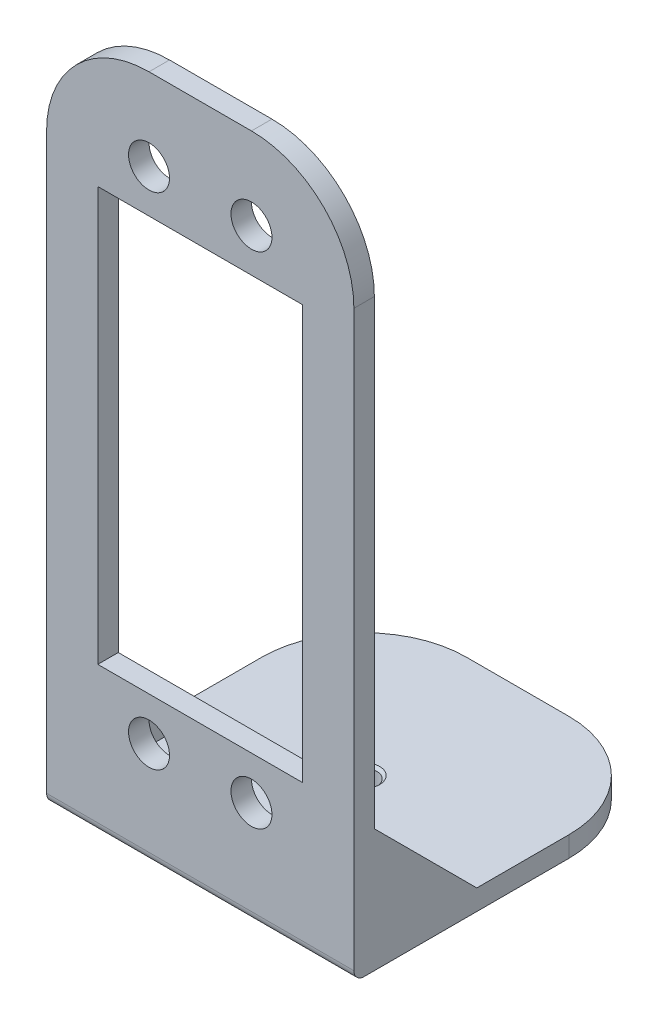
SolidWorks part; units mm, degrees
ref_plane "Front Plane" through (0, 0, 0) normal (0, 0, 1) x (1, 0, 0)
ref_plane "Top Plane" through (0, 0, 0) normal (0, 1, 0) x (1, 0, 0)
ref_plane "Right Plane" through (0, 0, 0) normal (1, 0, 0) x (0, 0, -1)
sketch "Sketch1" plane through (0, 0, 0) normal (0, 1, 0) x (1, 0, 0)
  line L1 (0, 0) -> (30, 0)
  line L2 (0, 0) -> (0, 30)
  line L3 (0, 30) -> (30, 30)
  line L4 (30, 0) -> (30, 30)
  dimension "D1" = 30
  dimension "D2" = 30
extrude "Boss-Extrude1" add sketch "Sketch1" along normal blind 2
sketch "Sketch2" plane through (0, 2, 0) normal (0, 1, 0) x (1, 0, 0)
  line L0 (30, 0) -> (30, 30) construction
  line L1 (0, 0) -> (30, 0)
  line L2 (0, 0) -> (0, 1)
  line L3 (0, 1) -> (30, 1)
  line L4 (30, 0) -> (30, 1)
  line L6 (0, 0) -> (30, 0)
  line L7 (0, 0) -> (0, -1)
  line L8 (0, -1) -> (30, -1)
  line L9 (30, 0) -> (30, -1)
  line M1 (0, 30) -> (0, 0)
  line M2 (0, 0) -> (30, 0)
  line M3 (30, 0) -> (30, 30)
  dimension "D1" = 1
  dimension "D2" = 1
extrude "Boss-Extrude2" add sketch "Sketch2" along normal blind 65 and the other way blind 2 contours L3 M1 M2 M3 | L9 L7 L8 M2 region at (15, 2, -0.5) region at (15, 2, 0.5)
fillet "Fillet1" radius 1 2 edges at (15, 0, 1) (15, 2, -1)
sketch "Sketch5" plane through (0, 2, 0) normal (0, 1, 0) x (1, 0, 0)
  line L0 (30, 2) -> (30, 30) construction
  line L1 (30, 30) -> (0, 30) construction
  circle A0 centre (15, 15) radius 1.5
  dimension "D1" = 15
  dimension "D2" = 15
hole_wizard "M3 Tapped Hole1" positions "Sketch6" profile "Sketch7" tap size "M3" standard "ISO" end condition through all
sketch "Sketch6" plane through (0, 2, 0) normal (0, 1, 0) x (1, 0, 0)
  point P0 (15, 15)
sketch "Sketch7" plane through (15, 2, -15) normal (1, 0, 0) x (0, 0, 1)
  line L0 (0, 0) -> (0, 2)
  line L1 (0, 2) -> (1.25, 2)
  line L2 (1.25, 2) -> (1.25, 0.275)
  line L3 (1.25, 0.275) -> (1.525, 0)
  line L5 (1.525, 0) -> (0, 0)
  line L6 (-1.25, 0.275) -> (-1.525, 0) construction
  line L11 (0, -6.35) -> (0, 107.95) construction
  dimension "Thru Tap Drill Dia." = 2.5
  dimension "Thru Tap Drill Depth" = 2
  dimension "Near C'Sink Dia." = 3.05
  dimension "Near C'Sink Angle" = 90
cosmetic thread "Hole Thread1" parameters "D2"=3
sketch "Sketch11" plane through (0, 0, 1) normal (0, 0, 1) x (1, 0, 0)
  line L0 (0, 1) -> (0, 67) construction
  line L1 (10, 59) -> (20, 59)
  line L2 (10, 59) -> (10, 10.2)
  line L3 (10, 10.2) -> (20, 10.2)
  line L4 (20, 59) -> (20, 10.2)
  line L5 (0, 67) -> (30, 67) construction
  line L6 (30, 3) -> (30, 67) construction
  line L7 (30, 0) -> (0, 0) construction
  line L8 (0, 54.8) -> (20, 54.8)
  line L9 (0, 54.8) -> (0, 14.4)
  line L10 (0, 14.4) -> (20, 14.4)
  line L11 (20, 54.8) -> (20, 14.4)
  line L13 (20, 54.8) -> (25, 54.8)
  line L14 (20, 54.8) -> (20, 14.4)
  line L15 (20, 14.4) -> (25, 14.4)
  line L16 (25, 54.8) -> (25, 14.4)
  line L17 (10, 14.4) -> (5, 14.4)
  line L18 (10, 14.4) -> (10, 54.8)
  line L19 (10, 54.8) -> (5, 54.8)
  line L20 (5, 14.4) -> (5, 54.8)
  circle A0 centre (10, 59) radius 2
  circle A1 centre (20, 59) radius 2
  circle A4 centre (10, 10.2) radius 2
  circle A5 centre (20, 10.2) radius 2
  dimension "D1" = 48.8
  dimension "D7" = 4.2
  dimension "D8" = 4.2
  dimension "D2" = 10
  dimension "D3" = 10
  dimension "D4" = 8
  dimension "D5" = 10.2
  dimension "D6" = 40.4
  dimension "D9" = 20
  dimension "D10" = 10
  dimension "D11" = 10
  dimension "D12" = 40.4
  dimension "D13" = 5
  dimension "D14" = 40.4
  dimension "D15" = 5
extrude "Cut-Extrude5" cut sketch "Sketch11" against normal blind 2 contours L3 A5 L4 | L4 A5 L3 | L2 A4 L3 | L3 A4 L2 | L2 A0 L1 | L1 A0 L2 | L1 A1 L4 | L4 A1 L1 | L2 L10 L4 L8 | L14 L13 L16 L15 | L18 L17 L20 L19 region at (9.7171, 59.2829, 1) region at (10.8488, 58.1512, 1) region at (20.2829, 59.2829, 1) region at (19.1512, 58.1512, 1) region at (15, 34.6, 1) region at (10.8488, 11.0488, 1) region at (9.7171, 9.9171, 1) region at (20.2829, 9.9171, 1) region at (19.1512, 11.0488, 1)
fillet "Fillet2" radius 10 4 edges at (0, 67, 0) (30, 67, 0) (30, 1, -30) (0, 1, -30)
sketch "Sketch12" plane through (0, 0, 0) normal (-1, 0, 0) x (0, 0, 1)
  line L0 (-1, 3) -> (-1, 57) construction
  line L1 (-1, 12) -> (-11, 12)
  line L2 (-1, 12) -> (-1, 2)
  line L3 (-1, 2) -> (-11, 2)
  line L4 (-11, 12) -> (-11, 2)
  line L5 (-20, 2) -> (-2, 2) construction
  line L6 (-1, 12) -> (-11, 2)
  circle A0 centre (-2, 3) radius 1
  line M1 (-2, 2) -> (-20, 2)
  line M7 (-1, 57) -> (-1, 3)
  arc M8 (-1, 3) -> (-2, 2) centre (-2, 3) cw
  dimension "D1" = 10
  dimension "D2" = 10
extrude "Boss-Extrude3" add sketch "Sketch12" against normal blind 2 contours A0 L6 M7 M1 | A0 M8 region at (0, 5.5048, -4.5048) region at (0, 3, -2)
ref_plane "Plane1" through (15, 0, 0) normal (1, 0, 0) x (0, 0, -1)
mirror "Mirror1" about plane through (15, 0, 0) normal (1, 0, 0) of "Boss-Extrude3"
